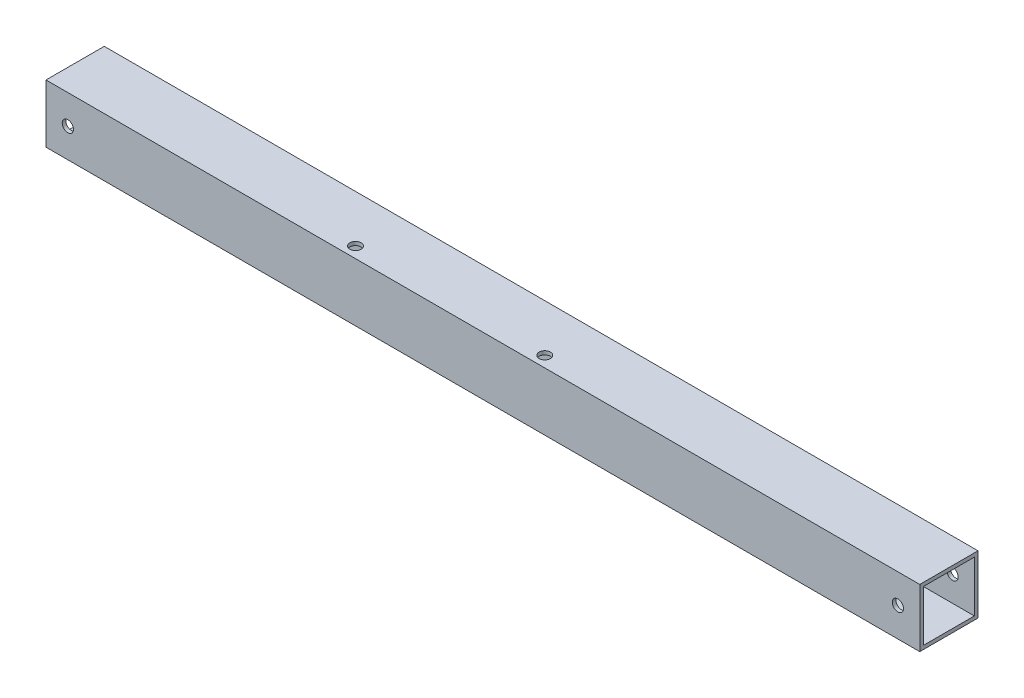
SolidWorks part; units mm, degrees
material "6061-T6 (SS)"
ref_plane "Front" through (0, 0, 0) normal (0, 0, 1) x (1, 0, 0)
ref_plane "Top" through (0, 0, 0) normal (0, 1, 0) x (1, 0, 0)
ref_plane "Right" through (0, 0, 0) normal (1, 0, 0) x (0, 0, -1)
sketch "Sketch1" plane through (0, 0, 0) normal (1, 0, 0) x (0, 0, -1)
  line L1 (-12.7, -12.7) -> (12.7, -12.7)
  line L2 (-12.7, -12.7) -> (-12.7, 12.7)
  line L3 (-12.7, 12.7) -> (12.7, 12.7)
  line L4 (12.7, -12.7) -> (12.7, 12.7)
  line L5 (-12.7, -12.7) -> (12.7, 12.7) construction
  line L6 (-12.7, 12.7) -> (12.7, -12.7) construction
  point P0 (0, 0)
  dimension "D1" = 25.4
extrude "Extrude-Thin1" add sketch "Sketch1" along normal blind 381 thin thin type one direction reverse wall 1.5875
sketch "Sketch4" plane through (0, 0, 12.7) normal (0, 0, 1) x (1, 0, 0)
  line L0 (0, 12.7) -> (0, -12.7) construction
  line L1 (381, 12.7) -> (381, -12.7) construction
  point P0 (9.525, 0)
  point P2 (371.475, 0)
  dimension "D1" = 9.525
  dimension "D2" = 9.525
hole_wizard "#10 (0.1935) Diameter Hole1" positions "Sketch4" profile "Sketch3" hole size "#10" standard "ANSI Inch" end condition through all
sketch "Sketch3" plane through (9.525, 0, 12.7) normal (1, 0, 0) x (0, -1, 0)
  line L0 (0, 0) -> (0, 25.4)
  line L1 (0, 25.4) -> (2.4574, 25.4)
  line L2 (2.4574, 25.4) -> (2.4574, 0)
  line L5 (2.4574, 0) -> (0, 0)
  line L11 (0, -6.35) -> (0, 107.95) construction
  dimension "Thru Hole Dia." = 4.9149
  dimension "Thru Hole Depth" = 25.4
sketch "Sketch7" plane through (0, 12.7, 0) normal (0, 1, 0) x (1, 0, 0)
  line L0 (381, -12.7) -> (0, -12.7) construction
  line L1 (0, 12.7) -> (0, -12.7) construction
  point P0 (130.175, -7.9375)
  point P2 (212.725, -7.9375)
  dimension "D1" = 4.7625
  dimension "D2" = 130.175
  dimension "D3" = 82.55
hole_wizard "#10 (0.1935) Diameter Hole2" positions "Sketch7" profile "Sketch6" hole size "#10" standard "ANSI Inch" end condition through all
sketch "Sketch6" plane through (130.175, 12.7, 7.9375) normal (1, 0, 0) x (0, 0, 1)
  line L0 (0, 0) -> (0, 25.4)
  line L1 (0, 25.4) -> (2.4574, 25.4)
  line L2 (2.4574, 25.4) -> (2.4574, 0)
  line L5 (2.4574, 0) -> (0, 0)
  line L11 (0, -6.35) -> (0, 107.95) construction
  dimension "Thru Hole Dia." = 4.9149
  dimension "Thru Hole Depth" = 25.4
